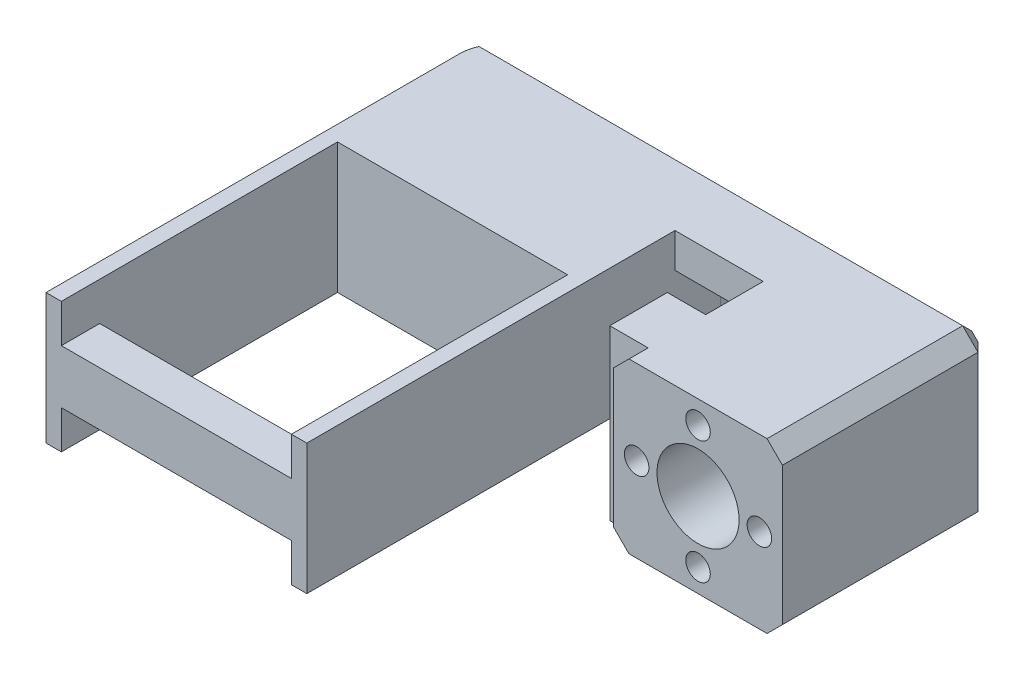
SolidWorks part; units mm, degrees
ref_plane "Płaszczyzna przednia" through (0, 0, 0) normal (0, 0, 1) x (1, 0, 0)
ref_plane "Płaszczyzna górna" through (0, 0, 0) normal (0, 1, 0) x (1, 0, 0)
ref_plane "Płaszczyzna prawa" through (0, 0, 0) normal (1, 0, 0) x (0, 0, -1)
sketch "Szkic2" plane through (0, 0, 0) normal (0, 1, 0) x (1, 0, 0)
  line L0 (0, 0) -> (0, 11.0602) construction
  line L5 (17, 19) -> (-17, 19)
  line L6 (17, 19) -> (17, -19)
  line L11 (17, -19) -> (-17, -19)
  line L12 (-17, 19) -> (-17, -19)
  line L13 (17, 19) -> (-17, -19) construction
  line L14 (17, -19) -> (-17, 19) construction
  line L16 (15, 17) -> (-15, 17)
  line L17 (15, 17) -> (15, -14)
  line L18 (15, -14) -> (-15, -14)
  line L19 (-15, 17) -> (-15, -14)
  line L20 (15, 17) -> (-15, -14) construction
  line L21 (15, -14) -> (-15, 17) construction
  point P0 (0, 0)
  point P5 (0, 1.5)
  dimension "D1" = 34
  dimension "D2" = 38
  dimension "D3" = 2
  dimension "D4" = 2
  dimension "D5" = 5
extrude "Dodanie-wyciągnięcie1" add sketch "Szkic2" along normal blind 17
sketch "Szkic6" plane through (0, 0, 14) normal (0, 0, -1) x (-1, 0, 0)
  line L0 (0, 17) -> (0, 0) construction
  line L1 (15, 17) -> (-15, 17) construction
  line L2 (15, 0) -> (-15, 0) construction
  line L3 (-15, 17) -> (-15, 0) construction
  line L4 (15, 5) -> (-15, 5)
  line L5 (15, 5) -> (15, 12)
  line L6 (15, 12) -> (-15, 12)
  line L7 (-15, 5) -> (-15, 12)
  line L8 (15, 5) -> (-15, 12) construction
  line L9 (15, 12) -> (-15, 5) construction
  line L11 (-15, 17) -> (15, 17)
  line L12 (-15, 17) -> (-15, 0)
  line L13 (-15, 0) -> (15, 0)
  line L14 (15, 17) -> (15, 0)
  point P6 (0, 8.5)
  line M9 (-15, 0) -> (15, 0)
  line M10 (15, 0) -> (15, 17)
  line M11 (15, 17) -> (-15, 17)
  line M12 (-15, 17) -> (-15, 0)
  dimension "D1" = 5
extrude "Wytnij-wyciągnięcie1" cut sketch "Szkic6" against normal blind 17 contours L6 M10 M11 M12 | L4 M10 M12 M9 region at (0, 2.5, 14) region at (0, 14.5, 14)
sketch "Szkic7" plane through (0, 0, -19) normal (0, 0, -1) x (-1, 0, 0)
  line L1 (-17, 17) -> (17, 17)
  line L2 (-17, 17) -> (-17, 0)
  line L3 (-17, 0) -> (17, 0)
  line L4 (17, 17) -> (17, 0)
extrude "Dodanie-wyciągnięcie2" add sketch "Szkic7" along normal blind 10
sketch "Szkic8" plane through (0, 0, -29) normal (0, 0, -1) x (-1, 0, 0)
  line L0 (-17, 17) -> (-17, 18) construction
  line L1 (-17, 17) -> (-24, 17)
  line L2 (-17, 17) -> (-17, 12.5)
  line L3 (-17, 12.5) -> (-24, 12.5)
  line L4 (-24, 17) -> (-24, 12.5)
  line L5 (-17, 17) -> (17, 17)
  line L6 (-17, 17) -> (-17, 0)
  line L7 (-17, 0) -> (17, 0)
  line L8 (17, 17) -> (17, 0)
  line L9 (-17, 18) -> (-22.5, 18) construction
  line L10 (-37.5, 18) -> (-37.5, -6) construction
  line L11 (-22.5, 18) -> (-52.5, 18) construction
  line L12 (-24, 17) -> (-37.5, 17)
  line L13 (-24, 12.5) -> (-26.9837, 2.7739)
  circle A0 centre (-37.5, 6) radius 5.35
  circle A1 centre (-37.5, 6) radius 11
  line M16 (-17, 17) -> (-17, 0)
  line M17 (-17, 0) -> (17, 0)
  line M18 (17, 0) -> (17, 17)
  line M19 (17, 17) -> (-17, 17)
  dimension "D6" = 10.7
  dimension "D1" = 4.5
  dimension "D2" = 7
  dimension "D3" = 5.5
  dimension "D4" = 1
  dimension "D5" = 24
  dimension "30" = 30
extrude "Dodanie-wyciągnięcie3" add sketch "Szkic8" along normal blind 10 contours A1 A0 | A1 L13 L4 L12 | L1 L4 L3 M16 | M19 M16 M17 M18 region at (20.5, 14.75, -29) region at (0, 8.5, -29) region at (27.368, 13.5434, -29) region at (29.9418, 13.5582, -29)
sketch "Szkic10" plane through (0, 0, -29) normal (0, 0, 1) x (1, 0, 0)
  circle A0 centre (37.5, 6) radius 5.35
  circle A1 centre (37.5, 6) radius 11
extrude "Dodanie-wyciągnięcie4" add sketch "Szkic10" along normal blind 17.5
sketch "Szkic11" plane through (0, 0, -39) normal (0, 0, -1) x (-1, 0, 0)
  circle A0 centre (-37.5, 6) radius 4.2
  circle A1 centre (-37.5, 6) radius 5.35
  dimension "D1" = 8.4
extrude "Dodanie-wyciągnięcie5" add sketch "Szkic11" against normal blind 16
sketch "Szkic13" plane through (0, 0, -11.5) normal (0, 0, 1) x (1, 0, 0)
  line L0 (37.5, 6) -> (37.5, 14) construction
  circle A0 centre (37.5, 6) radius 8
  circle A1 centre (37.5, 14) radius 1.6
  circle A2 centre (45.5, 6) radius 1.6
  circle A3 centre (37.5, -2) radius 1.6
  circle A4 centre (29.5, 6) radius 1.6
  point P16 (37.5, 6)
  dimension "D3" = 3.2
  dimension "D1" = 8
  dimension "D2" = 4
extrude "Wytnij-wyciągnięcie2" cut sketch "Szkic13" against normal blind 10 contours A0 A4 | A0 A4 | A1 L0 A0 | A0 A1 | L0 A1 A0 | A0 A2 | A0 A2 | A0 A3 | A0 A3 region at (36.844, 13.2929, -11.5) region at (38.156, 13.2929, -11.5) region at (37.5, 14.6494, -11.5) region at (30.2071, 6, -11.5) region at (28.8506, 6, -11.5) region at (46.1494, 6, -11.5) region at (44.7929, 6, -11.5) region at (37.5, -1.2929, -11.5) region at (37.5, -2.6494, -11.5)
sketch "Szkic16" plane through (0, 0, -39) normal (0, 0, -1) x (-1, 0, 0)
  line L0 (17, 17) -> (-37.5, 17) construction
  line L1 (-26.5, 17) -> (-48.5, 17)
  line L2 (-26.5, 17) -> (-26.5, -5)
  line L3 (-26.5, -5) -> (-48.5, -5)
  line L4 (-48.5, 17) -> (-48.5, -5)
  line L5 (-26.5, 17) -> (-48.5, -5) construction
  line L6 (-26.5, -5) -> (-48.5, 17) construction
  arc A0 (-37.5, 17) -> (-26.9837, 2.7739) centre (-37.5, 6) ccw construction
  circle A1 centre (-37.5, 6) radius 11
  point P0 (-37.5, 6)
  arc M5 (-37.5, 17) -> (-26.9837, 2.7739) centre (-37.5, 6) ccw
  line M6 (-26.9837, 2.7739) -> (-24, 12.5)
  line M11 (17, 17) -> (-37.5, 17)
extrude "Dodanie-wyciągnięcie6" add sketch "Szkic16" against normal up to surface (27.5 mm away) contours L1 L4 M5 | A1 L2 M11 | L3 L2 M6 M5 | L4 L3 M5 | A1 L2 M6 region at (28.957, 14.543, -39) region at (46.043, 14.543, -39) region at (26.5971, 4.3652, -39) region at (46.043, -2.543, -39) region at (28.9693, -2.5788, -39) up to face at (31.1, 6, -11.5)
chamfer "Sfazowanie1" distance 2 angle 45 4 edges at (26.5, -5, -25.25) (48.5, -5, -25.25) (26.5, 17, -20.25) (48.5, 17, -25.25)
chamfer "Sfazowanie2" distance 2 angle 45 3 edges at (17, 6.25, -39) (0, 0, -39) (-17, 8.5, -39)
chamfer "Sfazowanie3" distance 2 angle 45 9 edges at (19.5, 12.5, -39) (15.75, 17, -39) (47.5, 16, -39) (48.5, 6, -39) (47.5, -4, -39) (37.5, -5, -39) (27.5, -4, -39) (26.5, 0.6753, -39) (25.25, 8.4253, -39)
fillet "Zaokrąglenie1" radius 5 2 edges at (17, 6.25, -37) (-17, 8.5, -37)
ref_plane "Płaszczyzna1" through (0, 0, -21.5) normal (0, 0, 1) x (1, 0, 0)
sketch "Szkic18" plane through (0, 0, -21.5) normal (0, 0, 1) x (1, 0, 0)
  line L0 (28.5, 17) -> (23.5, 17)
  line L2 (17, 17) -> (28.5, 17) construction
  line L3 (23.5, 17) -> (23.5, -5)
  line L4 (23.5, -5) -> (28.5, -5)
  line L6 (26.5, 15) -> (26.5, -3) construction
  line L7 (26.5, -3) -> (28.5, -5) construction
  line L8 (28.5, 17) -> (26.5, 15) construction
  line L9 (26.5, -3) -> (28.5, -5)
  line L10 (26.5, 15) -> (26.5, -3)
  line L11 (28.5, 17) -> (26.5, 15)
  dimension "D1" = 3
extrude "Dodanie-wyciągnięcie8" add sketch "Szkic18" along normal blind 7.5
